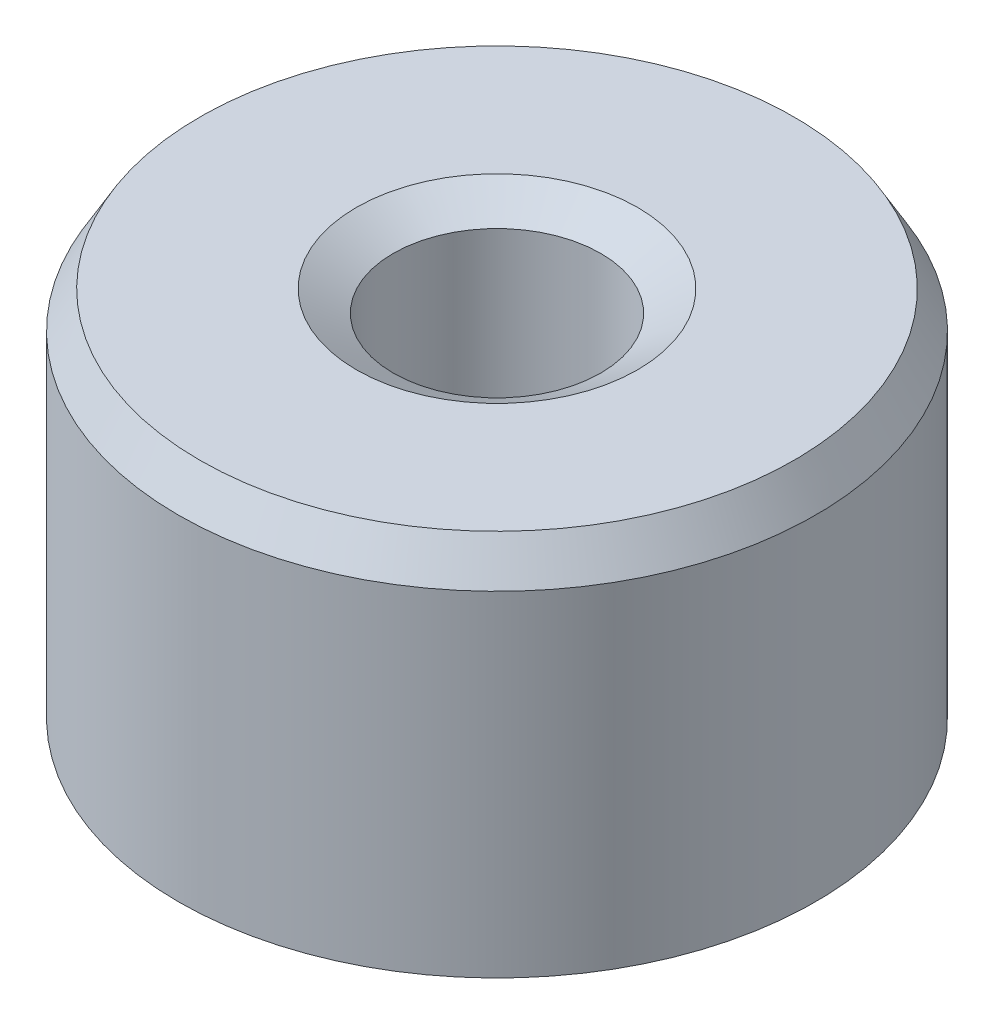
SolidWorks part; units mm, degrees
ref_plane "Front Plane" through (0, 0, 0) normal (0, 0, 1) x (1, 0, 0)
ref_plane "Top Plane" through (0, 0, 0) normal (0, 1, 0) x (1, 0, 0)
ref_plane "Right Plane" through (0, 0, 0) normal (1, 0, 0) x (0, 0, -1)
sketch "Sketch1" plane through (0, 0, 0) normal (0, 1, 0) x (1, 0, 0)
  circle A0 centre (0, 0) radius 5
  dimension "SLEEVE_OD" = 10
extrude "Boss-Extrude1" add sketch "Sketch1" along normal blind 6.1706
sketch "Sketch2" plane through (0, 0, 0) normal (0, 1, 0) x (1, 0, 0)
  circle A0 centre (0, 0) radius 1.6282
  dimension "BORE_D" = 3.2564
extrude "Cut-Extrude1" cut sketch "Sketch2" along normal through all
chamfer "Chamfer1" distance 0.5794 angle 30 4 edges at (0, 6.1706, 1.6282) (0, 0, 1.6282) (0, 0, 5) (0, 6.1706, 5) first distance on face at (0, 6.1706, 1.6282) first distance on face at (0, 0, 1.6282) first distance on face at (0, 6.1706, 5)
